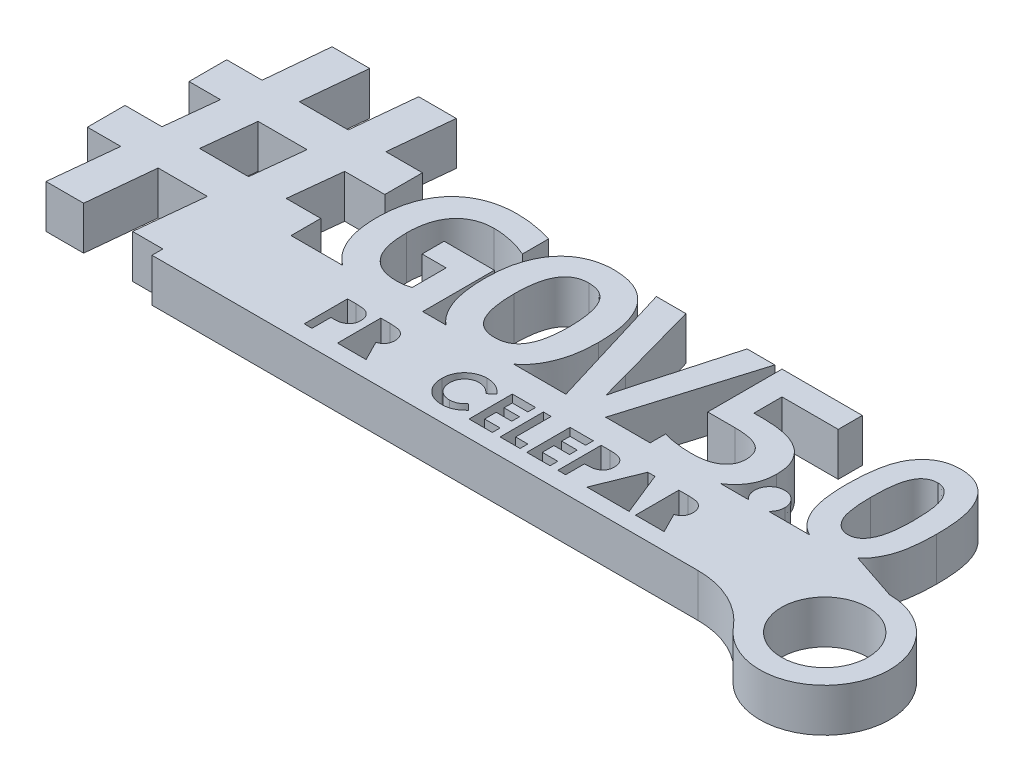
SolidWorks part; units mm, degrees
ref_plane "Front Plane" through (0, 0, 0) normal (0, 0, 1) x (1, 0, 0)
ref_plane "Top Plane" through (0, 0, 0) normal (0, 1, 0) x (1, 0, 0)
ref_plane "Right Plane" through (0, 0, 0) normal (1, 0, 0) x (0, 0, -1)
sketch "Sketch1" plane through (0, 0, 0) normal (0, 1, 0) x (1, 0, 0)
  text T0 "<b>#</b>" font "Consolas" height 30
extrude "Boss-Extrude1" add sketch "Sketch1" along normal blind 5
sketch "Sketch2" plane through (0, 5, 0) normal (0, 1, 0) x (1, 0, 0)
  text T0 "<b>GOV5</b>" font "Consolas" height 16
extrude "Boss-Extrude2" add sketch "Sketch2" against normal blind 5 separate body
sketch "Sketch3" plane through (0, 5, 0) normal (0, 1, 0) x (1, 0, 0)
  line L0 (62.3851, 9.3354) -> (58.3996, 9.3354) construction
  line L1 (20.2873, 10.3354) -> (90.3172, 10.3354)
  line L2 (20.2873, 10.3354) -> (20.2873, 0.3354)
  line L3 (20.2873, 0.3354) -> (90.3172, 0.3354)
  line L4 (90.3172, 10.3354) -> (90.3172, 0.3354)
  dimension "D1" = 10
  dimension "D2" = 1
extrude "Boss-Extrude3" add sketch "Sketch3" against normal blind 5
sketch "Sketch4" plane through (0, 5, 0) normal (0, 1, 0) x (1, 0, 0)
  text T0 "." font "Century Gothic" height 16
extrude "Boss-Extrude5" add sketch "Sketch4" against normal blind 5
sketch "Sketch5" plane through (0, 5, 0) normal (0, 1, 0) x (1, 0, 0)
  text T0 "0" font "Century Gothic" height 15
extrude "Boss-Extrude6" add sketch "Sketch5" against normal blind 5
sketch "Sketch8" plane through (0, 5, 0) normal (0, 1, 0) x (1, 0, 0)
  circle A0 centre (96.8593, 1.47) radius 7.5
  circle A1 centre (96.8593, 1.47) radius 5
  dimension "D1" = 10
  dimension "D2" = 15
extrude "Boss-Extrude9" add sketch "Sketch8" against normal blind 5 contours A0 | A1
fillet "Fillet1" radius 10 1 edges at (89.4456, 2.5, -0.3354)
fillet "Fillet2" radius 10 1 edges at (90.3172, 2.5, -5.1375)
sketch "Sketch10" plane through (0, 5, 0) normal (0, 1, 0) x (1, 0, 0)
  line L1 (96.8593, 8.97) -> (91.345, 10.8091)
  line L2 (91.345, 10.8091) -> (90.3172, 10.2035)
  line L3 (90.3172, 10.2035) -> (91.1882, 6.19)
  line L4 (91.1882, 6.19) -> (96.8593, 8.97)
  arc A0 (91.0732, -3.302) -> (96.1737, 8.9386) centre (96.8593, 1.47) ccw construction
  spline S0 degree 3 poles (93.507, 17.759) (93.5056, 17.5166) (93.5028, 17.0455) (93.4728, 16.36) (93.4212, 15.7157) (93.3546, 15.1129) (93.2635, 14.5517) (93.1567, 14.0307) (93.0298, 13.5502) (92.8766, 13.1112) (92.7118, 12.7066) (92.5304, 12.3316) (92.3356, 11.9852) (92.1319, 11.6621) (91.9081, 11.3719) (91.6751, 11.1047) (91.4227, 10.8707) (91.1617, 10.6578) (90.8823, 10.4739) (90.6012, 10.3204) (90.4082, 10.2389) (90.3172, 10.2035) knots 0 0 0 0 0.068491 0.133077 0.193829 0.251083 0.304401 0.354408 0.401295 0.444701 0.485692 0.524676 0.562307 0.597947 0.632474 0.665752 0.697985 0.729586 0.760825 0.792355 0.819946 0.819946 0.819946 0.819946 construction
  point P3 (91.345, 10.8091)
extrude "Boss-Extrude11" add sketch "Sketch10" against normal blind 5 contours L1 L2 L3 L4
sketch "Sketch11" plane through (0, 5, 0) normal (0, 1, 0) x (1, 0, 0)
  text T0 "<b>PR   CELEPAR</b>" font "Century Gothic" height 5
extrude "Cut-Extrude1" cut sketch "Sketch11" against normal blind 10
sketch "Sketch12" plane through (0, 5, 0) normal (0, 1, 0) x (1, 0, 0)
  line L0 (69.9603, 3.8463) -> (72.4847, 3.8463)
  line L1 (74.637, 6.5758) -> (76.6823, 6.5758)
  line L2 (74.637, 6.5758) -> (74.637, 5.0712)
  line L3 (74.637, 5.0712) -> (76.6823, 5.0712)
  line L4 (76.6823, 6.5758) -> (76.6823, 5.0712)
  line L5 (65.7686, 6.5758) -> (67.5053, 6.5758)
  line L6 (65.7686, 6.5758) -> (65.7686, 5.0712)
  line L7 (65.7686, 5.0712) -> (67.5053, 5.0712)
  line L8 (67.5053, 6.5758) -> (67.5053, 5.0712)
  line L9 (72.4847, 3.8463) -> (71.2225, 6.5758)
  line L10 (71.2225, 6.5758) -> (69.9603, 3.8463)
  line L11 (40.6846, 6.3674) -> (40.6846, 5.3418)
  line L12 (40.6846, 5.3418) -> (42.1348, 5.3418)
  line L13 (42.1348, 5.3418) -> (42.1348, 6.3674)
  line L14 (42.1348, 6.3674) -> (40.6846, 6.3674)
  line L15 (36.8384, 6.3674) -> (36.8384, 5.3418)
  line L16 (37.1209, 6.3674) -> (36.8384, 6.3674) construction
  line L17 (36.8384, 5.3418) -> (37.1559, 5.3418) construction
  line L18 (36.8384, 6.3674) -> (36.8384, 5.3418) construction
  line L19 (36.8384, 5.3418) -> (38.1863, 5.3418)
  line L20 (38.1863, 5.3418) -> (38.1863, 6.3674)
  line L21 (38.1863, 6.3674) -> (36.8384, 6.3674)
extrude "Cut-Extrude2" cut sketch "Sketch12" against normal blind 10
sketch "Sketch14" plane through (0, 5, 0) normal (0, 1, 0) x (1, 0, 0)
  line L0 (74.915, 2.2649) -> (77.0127, 2.2649)
  line L1 (75.1077, 2.2649) -> (74.2102, 2.2649) construction
  line L2 (77.5115, 2.2649) -> (76.5139, 2.2649) construction
  line L3 (77.0127, 2.2649) -> (75.4804, 5.1419)
  line L4 (75.4804, 5.1419) -> (74.915, 5.1419)
  line L5 (74.915, 5.1419) -> (74.915, 2.2649)
  line L6 (72.5145, 2.2649) -> (69.5588, 2.2649)
  line L7 (69.5588, 2.2649) -> (69.9474, 3.2905)
  line L8 (69.9474, 3.2905) -> (72.1259, 3.2905)
  line L9 (72.1259, 3.2905) -> (72.5145, 2.2649)
  line L10 (40.6846, 2.2649) -> (42.0908, 2.2649)
  line L11 (42.0908, 2.2649) -> (40.9891, 4.4444)
  line L12 (40.9891, 4.4444) -> (40.6846, 4.4444)
  line L13 (40.6846, 4.4444) -> (40.6846, 2.2649)
extrude "Cut-Extrude3" cut sketch "Sketch14" against normal blind 10
